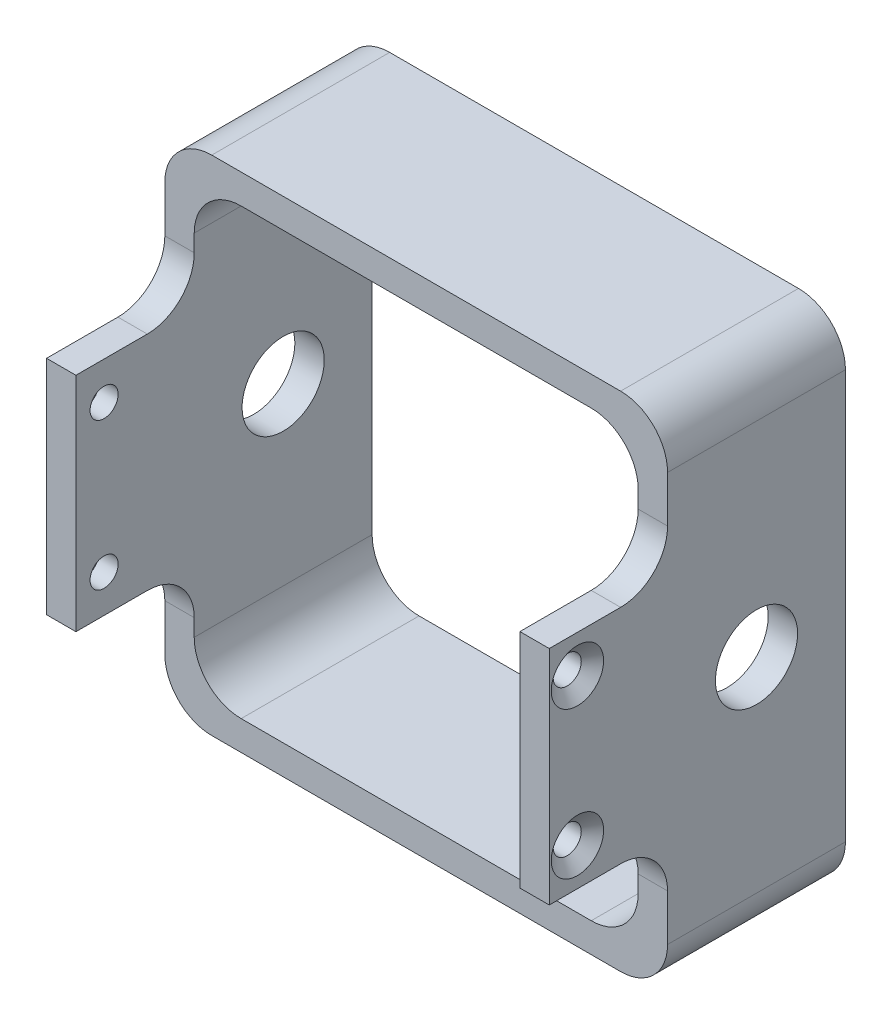
SolidWorks part; units mm, degrees
ref_plane "Front Plane" through (0, 0, 0) normal (0, 0, 1) x (1, 0, 0)
ref_plane "Top Plane" through (0, 0, 0) normal (0, 1, 0) x (1, 0, 0)
ref_plane "Right Plane" through (0, 0, 0) normal (1, 0, 0) x (0, 0, -1)
sketch "Sketch1" plane through (0, 0, 0) normal (0, 0, 1) x (1, 0, 0)
  line L0 (55, 0) -> (-55, 0) construction
  line L1 (-34.0042, -34.0043) -> (34.0043, -34.0043)
  line L2 (-34.0042, -34.0043) -> (-34.0043, 34.0042)
  line L3 (-34.0043, 34.0042) -> (34.0042, 34.0042)
  line L4 (34.0043, -34.0043) -> (34.0042, 34.0042)
  line L5 (-34.0042, -34.0043) -> (34.0042, 34.0042) construction
  line L6 (-34.0043, 34.0042) -> (34.0043, -34.0043) construction
  line L7 (0, -55) -> (0, 55) construction
  line L9 (-30.0292, -30.0292) -> (30.0291, -30.0292)
  line L10 (-30.0292, -30.0292) -> (-30.0292, 30.0291)
  line L11 (-30.0292, 30.0291) -> (30.0291, 30.0291)
  line L12 (30.0291, -30.0292) -> (30.0291, 30.0291)
  line L13 (-30.0292, -30.0292) -> (30.0291, 30.0291) construction
  line L14 (-30.0292, 30.0291) -> (30.0291, -30.0292) construction
  point P0 (0, 0)
  point P10 (0, 0)
  dimension "D1" = 68.0085
  dimension "D2" = 68.0085
  dimension "D3" = 60.0583
  dimension "D4" = 60.0583
extrude "Boss-Extrude1" add sketch "Sketch1" along normal blind 24.0665
sketch "Sketch3" plane through (34.0042, 0, 0) normal (1, 0, 0) x (0, 0, -1)
  line L0 (13.2366, 0) -> (-13.2366, 0) construction
  line L1 (-24.0665, 34.0042) -> (0, 34.0042) construction
  point P0 (-12.0333, 0)
  point P5 (-12.0333, 34.0042)
hole_wizard "7/16 (0.4375) Diameter Hole1" positions "Sketch4" profile "Sketch5" hole size "7/16" standard "ANSI Inch" end condition through all
sketch "Sketch4" plane through (34.0042, 0, 0) normal (1, 0, 0) x (0, 0, -1)
  point P0 (-12.0333, 0)
sketch "Sketch5" plane through (34.0042, 0, 12.0333) normal (0, 1, 0) x (0, 0, -1)
  line L0 (0, 0) -> (0, 68.0085)
  line L1 (0, 68.0085) -> (5.5562, 68.0085)
  line L2 (5.5562, 68.0085) -> (5.5562, 0)
  line L5 (5.5562, 0) -> (0, 0)
  line L11 (0, -6.35) -> (0, 107.95) construction
  dimension "Thru Hole Dia." = 11.1125
  dimension "Thru Hole Depth" = 68.0085
sketch "Sketch10" plane through (-34.0042, 0, 0) normal (-1, 0, 0) x (0, 0, 1)
  line L0 (40.0685, 15.0241) -> (40.0685, -15.0241)
  line L1 (13.2366, 0) -> (-13.2366, 0) construction
  line L2 (24.0665, 34.0042) -> (24.0665, -34.0043) construction
  line L3 (40.0685, 15.0241) -> (24.0665, 15.0241)
  line L4 (24.0665, 15.0241) -> (24.0665, -15.0241)
  line L5 (24.0665, -15.0241) -> (40.0685, -15.0241)
  point P3 (40.0685, 0)
  dimension "D1" = 30.0482
  dimension "D2" = 16.002
extrude "Boss-Extrude2" add sketch "Sketch10" against normal blind 3.9751 contours L5 L0 L3 L4
fillet "Fillet1" radius 6.35 2 edges at (-32.0167, -15.0241, 24.0665) (-32.0167, 15.0241, 24.0665)
mirror "Mirror1" about plane through (0, 0, 0) normal (1, 0, 0) of "Boss-Extrude2", "Fillet1"
fillet "Fillet2" radius 6.35 4 edges at (-34.0042, -34.0043, 12.0333) (34.0043, -34.0043, 12.0333) (-34.0043, 34.0042, 12.0333) (34.0042, 34.0042, 12.0333)
fillet "Fillet3" radius 6.35 4 edges at (-30.0292, -30.0292, 12.0333) (30.0291, -30.0292, 12.0333) (-30.0292, 30.0291, 12.0333) (30.0291, 30.0291, 12.0333)
sketch "Sketch11" plane through (-34.0042, 0, 0) normal (-1, 0, 0) x (0, 0, 1)
  line L0 (40.0685, 15.0241) -> (30.4165, 15.0241) construction
  line L1 (30.4165, -15.0241) -> (40.0685, -15.0241) construction
  line L2 (40.0685, 15.0241) -> (40.0685, -15.0241) construction
  point P0 (36.2585, 9.9441)
  point P1 (36.2585, -9.9441)
  dimension "D1" = 5.08
  dimension "D2" = 5.08
  dimension "D3" = 3.81
hole_wizard "CSK for #6 Flat Head Machine Screw (100)1" positions "Sketch12" profile "Sketch14" countersink size "#6" standard "ANSI Inch"
sketch "Sketch12" plane through (-34.0042, 0, 0) normal (-1, 0, 0) x (0, 0, 1)
  point P0 (36.2585, 9.9441)
  point P3 (36.2585, -9.9441)
sketch "Sketch14" plane through (-34.0042, 9.9441, 36.2585) normal (0, 1, 0) x (0, 0, 1)
  line L0 (0, 0) -> (0, 10.5388)
  line L1 (0, 10.5388) -> (1.8986, 9.398)
  line L2 (1.8986, 9.398) -> (1.8986, 1.38)
  line L3 (1.8986, 1.38) -> (3.5433, 0)
  line L5 (3.5433, 0) -> (0, 0)
  line L6 (-1.8986, 1.38) -> (-3.5433, 0) construction
  line L10 (0, 10.5388) -> (-1.8987, 9.398) construction
  line L11 (0, -6.35) -> (0, 107.95) construction
  dimension "Hole Dia." = 3.7973
  dimension "Hole Depth" = 9.398
  dimension "Near C'Sink Dia." = 7.0866
  dimension "Near C'Sink Angle" = 100
  dimension "Drill Angle" = 118
mirror "Mirror2" about plane through (0, 0, 0) normal (1, 0, 0) of "CSK for #6 Flat Head Machine Screw (100)1"
